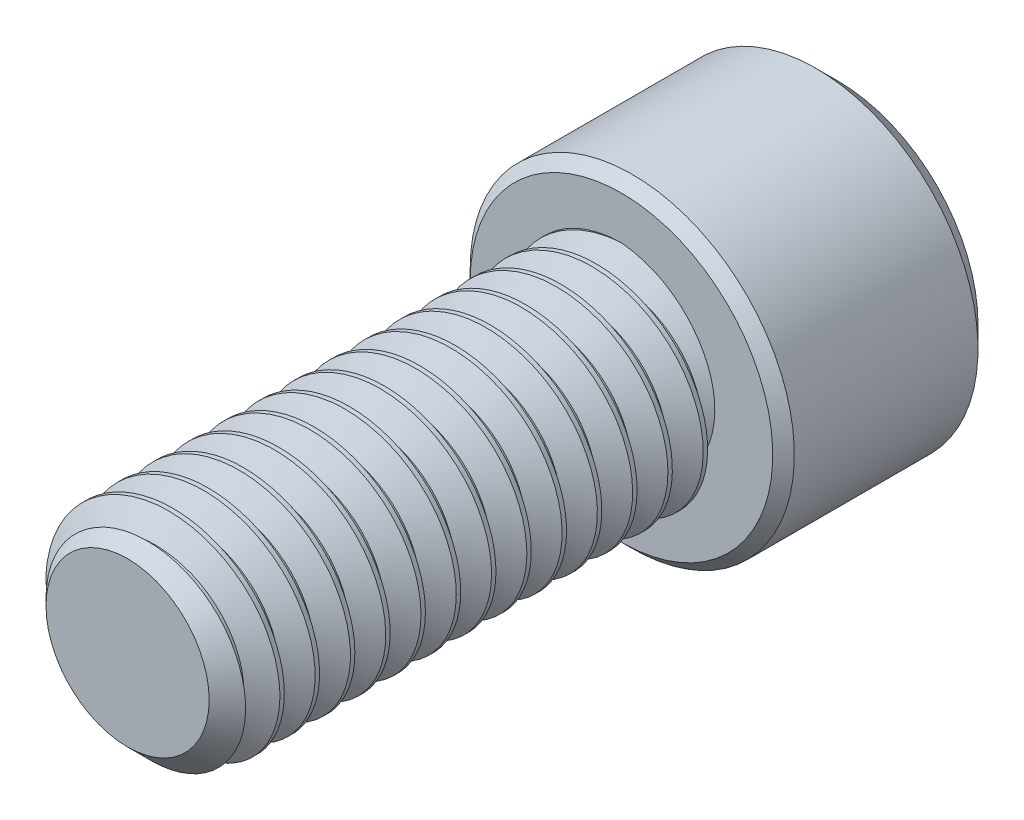
SolidWorks part; units mm, degrees
material "Alloy Steel"
ref_plane "Front Plane" through (0, 0, 0) normal (0, 0, 1) x (1, 0, 0)
ref_plane "Top Plane" through (0, 0, 0) normal (0, 1, 0) x (1, 0, 0)
ref_plane "Right Plane" through (0, 0, 0) normal (1, 0, 0) x (0, 0, -1)
sketch "Sketch1" plane through (0, 0, 0) normal (0, 0, 1) x (1, 0, 0)
  line L0 (0, 5.5562) -> (0, -5.5562) construction
  circle A0 centre (0, 0) radius 5.5562
  dimension "OD" = 11.1125
extrude "Extrude1" add sketch "Sketch1" against normal blind 25.4
sketch "Sketch2" plane through (0, 0, 0) normal (0, 0, 1) x (1, 0, 0)
  circle A0 centre (0, 0) radius 5.5562 construction
  circle A1 centre (0, 0) radius 5.5562
curve "Helix/Spiral1" pitch 1.8143 height 27.2143 turns 15 parameters "pitch"=1.8143
chamfer "Chamfer3" distance 1.3607 angle 45 1 edges at (5.5562, 0, 0)
sketch "Sketch3" plane through (0, 0, 0) normal (1, 0, 0) x (0, 0, -1)
  line L0 (-1.5875, 5.5562) -> (-0.9071, 4.3778)
  line L1 (-0.9071, 4.3778) -> (-0.6804, 4.3778)
  line L2 (-0.6804, 4.3778) -> (0, 5.5562)
  line L3 (-1.5875, 5.5562) -> (0, 5.5562)
  line L4 (-0.7938, 5.5562) -> (-0.7938, 4.3778) construction
  line L5 (-1.2473, 4.967) -> (-0.3402, 4.967) construction
  line L6 (0, 5.5562) -> (0, -5.5562) construction
  dimension "D1" = 0.2268
  dimension "D2" = 0.9071
  dimension "D3" = 60
sweep "Cut-Sweep1" cut profiles "Sketch3" path "Helix/Spiral1"
sketch "Sketch6" plane through (0, 0, -25.4) normal (0, 0, -1) x (-1, 0, 0)
  circle A0 centre (0, 0) radius 8.3344
  dimension "head dia" = 16.6687
extrude "Extrude2" add sketch "Sketch6" along normal blind 11.1125
sketch "Sketch7" plane through (0, 0, -36.5125) normal (0, 0, -1) x (-1, 0, 0)
  line L1 (0, 5.4993) -> (-4.7625, 2.7496)
  line L2 (-4.7625, 2.7496) -> (-4.7625, -2.7496)
  line L3 (-4.7625, -2.7496) -> (0, -5.4993)
  line L4 (0, -5.4993) -> (4.7625, -2.7496)
  line L5 (4.7625, -2.7496) -> (4.7625, 2.7496)
  line L6 (4.7625, 2.7496) -> (0, 5.4993)
  circle A0 centre (0, 0) radius 4.7625 construction
  dimension "hex dia" = 9.525
extrude "Cut-Extrude1" cut sketch "Sketch7" against normal blind 7.1438
sketch "Sketch8" plane through (0, 0, -36.5125) normal (0, 0, -1) x (-1, 0, 0)
  circle A0 centre (0, 0) radius 5.4993
extrude "Cut-Extrude2" cut sketch "Sketch8" against normal blind 1.1112 draft 45
chamfer "Chamfer1" distance 1.1112 angle 45 1 edges at (-8.3344, 0, -36.5125)
chamfer "Chamfer2" distance 0.5556 angle 45 1 edges at (-8.3344, 0, -25.4)
sketch "Sketch9" plane through (0, 0, 0) normal (1, 0, 0) x (0, 0, -1)
  line L0 (0, 5.5562) -> (0, -5.5562) construction
  line L1 (9.9786, 5.5562) -> (9.9786, -5.5562) construction
  line L2 (25.4, 8.3344) -> (25.4, -8.3344) construction
  line L3 (36.5125, 8.3344) -> (36.5125, -8.3344) construction
  line L4 (36.5125, 0) -> (0, 0) construction
  dimension "D1" = 9.9786
  dimension "D2" = 11.1125
  dimension "D3" = 16.6687
  dimension "D4" = 25.4
equation "\"D3@Helix/Spiral1\" = \"screw length@Extrude1\"+\"pitch@Helix/Spiral1\""
equation "\"D1@Sketch3\" = \"pitch@Helix/Spiral1\"*.125"
equation "\"D2@Sketch3\" = \"pitch@Helix/Spiral1\"*.5"
equation "\"D1@Cut-Extrude1\" = \"hex dia@Sketch7\"*.75"
equation "\"D1@Chamfer1\" = \"head depth@Extrude2\"/10"
equation "\"D1@Sketch9\" = \"pitch@Helix/Spiral1\"*5.5"
equation "\"D1@Chamfer2\" = \"D1@Chamfer1\"/2"
equation "\"D1@Cut-Extrude2\" = \"D1@Chamfer2\"*2"
equation "\"D1@Chamfer3\" = \"pitch@Helix/Spiral1\"*.750"
equation "\"D2@Sketch9\" = \"head depth@Extrude2\""
equation "\"D3@Sketch9\" = \"head dia@Sketch6\""
equation "\"D4@Sketch9\" = \"screw length@Extrude1\""
